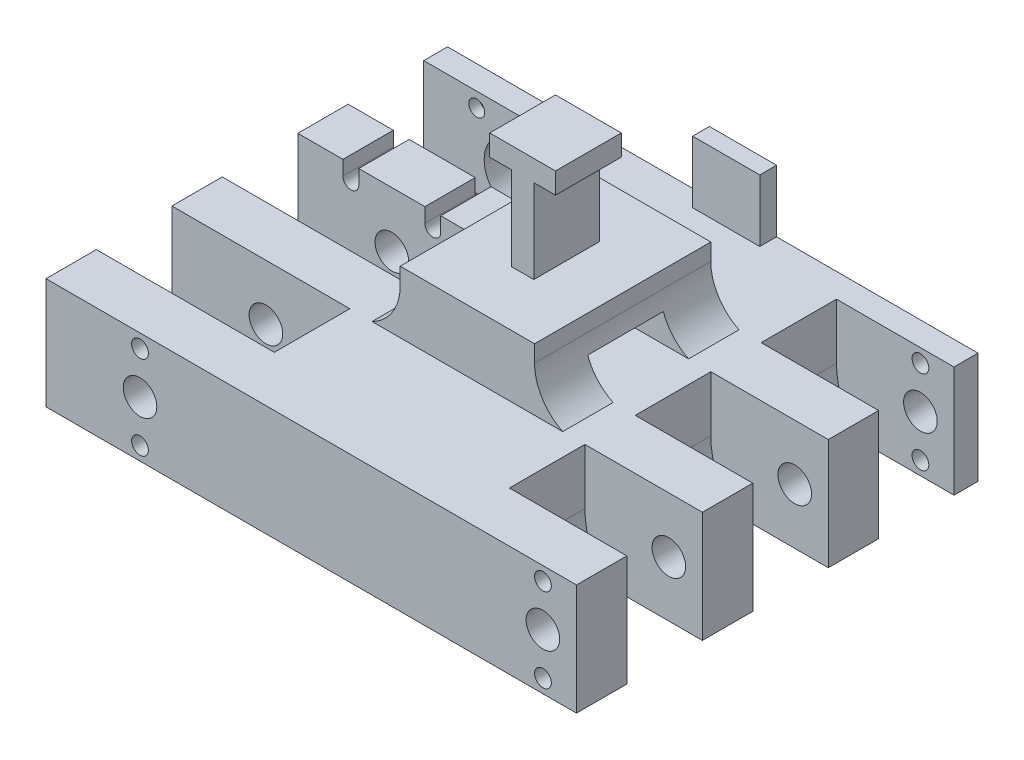
SolidWorks part; units mm, degrees
note: '?' marks a value the reader was unsure of. The reader was unsure of these and kept them because the rebuilt part matched: shared geometry of "Sketch17<3>", "Sketch17<5>", "Sketch17<6>", "Sketch2<4>", "Sketch2<5>".
ref_plane "Front Plane" through (0, 0, 0) normal (0, 0, 1) x (1, 0, 0)
ref_plane "Top Plane" through (0, 0, 0) normal (0, 1, 0) x (1, 0, 0)
ref_plane "Right Plane" through (0, 0, 0) normal (1, 0, 0) x (0, 0, -1)
sketch "Sketch1" plane through (0, 0, 0) normal (0, 1, 0) x (1, 0, 0)
  line L0 (-25.4, 0) -> (-25.4, 28.575)
  line L1 (-25.4, 123.825) -> (25.4, 123.825)
  line L2 (-25.4, 28.575) -> (-127, 28.575)
  line L3 (-25.4, 0) -> (25.4, 0)
  line L4 (0, 123.825) -> (0, 0) construction
  line L5 (-127, 28.575) -> (-127, 47.625)
  line L6 (-127, 47.625) -> (-25.4, 47.625)
  line L7 (-25.4, 47.625) -> (-25.4, 76.2)
  line L8 (-25.4, 76.2) -> (-127, 76.2)
  line L9 (-127, 76.2) -> (-127, 95.25)
  line L10 (-127, 95.25) -> (-25.4, 95.25)
  line L11 (-25.4, 95.25) -> (-25.4, 123.825)
  line L12 (25.4, 95.25) -> (25.4, 123.825)
  line L13 (127, 95.25) -> (25.4, 95.25)
  line L14 (127, 76.2) -> (127, 95.25)
  line L15 (25.4, 76.2) -> (127, 76.2)
  line L16 (25.4, 47.625) -> (25.4, 76.2)
  line L17 (127, 47.625) -> (25.4, 47.625)
  line L18 (127, 28.575) -> (127, 47.625)
  line L19 (25.4, 28.575) -> (127, 28.575)
  line L20 (25.4, 0) -> (25.4, 28.575)
  point P1 (-76.2, 28.575)
  dimension "D1" = 28.575
  dimension "D2" = 19.05
  dimension "D3" = 28.575
  dimension "D4" = 19.05
  dimension "D5" = 28.575
  dimension "D6" = 76.2
  dimension "D7" = 101.6
extrude "Boss-Extrude1" add sketch "Sketch1" along normal blind 38.1
sketch "Sketch2" plane through (0, 0, -28.575) normal (0, 0, 1) x (1, 0, 0)
  line L0 (-127, 38.1) -> (-127, 0) construction
  line L1 (-127, 0) -> (-25.4, 0) construction
  line L2 (0, 38.1) -> (0, 0) construction
  line L3 (-25.4, 38.1) -> (25.4, 38.1) construction
  circle A0 centre (-76.2, 19.05) radius 6.35
  circle A1 centre (76.2, 19.05) radius 6.35
  point P5 (-127, 19.05)
  point P8 (-76.2, 0)
  dimension "D1" = 12.7
extrude "Cut-Extrude1" cut sketch "Sketch2" against normal blind 254 and the other way through all contours A0 | A1
ref_plane "Plane1" through (0, 0, -61.9125) normal (0, 0, 1) x (1, 0, 0)
ref_axis "Axis3" through (0, 40.005, -61.9125) along (0, -1, 0)?
sketch "Sketch12" plane through (0, 38.1, 0) normal (0, 1, 0) x (1, 0, 0)
  line L1 (25.4, 28.575) -> (-25.4, 28.575)
  line L2 (25.4, 28.575) -> (25.4, 47.625)
  line L3 (25.4, 47.625) -> (-25.4, 47.625)
  line L4 (-25.4, 28.575) -> (-25.4, 47.625)
  line L5 (25.4, 76.2) -> (-25.4, 76.2)
  line L6 (25.4, 76.2) -> (25.4, 95.25)
  line L7 (25.4, 95.25) -> (-25.4, 95.25)
  line L8 (-25.4, 76.2) -> (-25.4, 95.25)
extrude "Boss-Extrude6" add sketch "Sketch12" along normal blind 12.7
sketch "Sketch13" plane through (0, 50.8, 0) normal (0, 1, 0) x (1, 0, 0)
  line L1 (25.4, 28.575) -> (-25.4, 28.575)
  line L2 (25.4, 28.575) -> (25.4, 95.25)
  line L3 (25.4, 95.25) -> (-25.4, 95.25)
  line L4 (-25.4, 28.575) -> (-25.4, 95.25)
extrude "Boss-Extrude7" add sketch "Sketch13" along normal blind 12.7
sketch "Sketch5" plane through (0, 63.5, 0) normal (0, 1, 0) x (1, 0, 0)
  line L1 (4.2333, 74.3585) -> (-4.2333, 74.3585)
  line L2 (4.2333, 74.3585) -> (4.2333, 49.4665)
  line L3 (4.2333, 49.4665) -> (-4.2333, 49.4665)
  line L4 (-4.2333, 74.3585) -> (-4.2333, 49.4665)
  point P4 (-4.2333, 61.9125)
  point P5 (0, 74.3585)
  dimension "D1" = 24.892
  dimension "D2" = 8.4667
extrude "Boss-Extrude8" add sketch "Sketch5" along normal blind 31.75 contours L4 L3 L2 L1
sketch "Sketch15" plane through (0, 95.25, 0) normal (0, 1, 0) x (1, 0, 0)
  line L1 (-12.446, 74.3585) -> (12.446, 74.3585)
  line L2 (-12.446, 74.3585) -> (-12.446, 49.4665)
  line L3 (-12.446, 49.4665) -> (12.446, 49.4665)
  line L4 (12.446, 74.3585) -> (12.446, 49.4665)
  point P4 (-12.446, 61.9125)
  point P6 (0, 49.4665)
  dimension "D1" = 24.892
  dimension "D2" = 24.892
extrude "Boss-Extrude9" add sketch "Sketch15" along normal blind 7.9375 contours L1 L4 L3 L2
sketch "Sketch17" plane through (0, 0, -123.825) normal (0, 0, -1) x (-1, 0, 0)
  line L0 (55.2, -1.95) -> (-25.4, -1.95)
  line L1 (60.7, 34.55) -> (91.7, 34.55) construction
  line L2 (60.7, 34.55) -> (60.7, 3.55) construction
  line L3 (60.7, 3.55) -> (91.7, 3.55) construction
  line L4 (91.7, 34.55) -> (91.7, 3.55) construction
  line L5 (55.2, 40.05) -> (97.2, 40.05)
  line L6 (-25.4, 38.1) -> (-25.4, 0) construction
  line L7 (55.2, -1.95) -> (97.2, -1.95)
  line L8 (97.2, 40.05) -> (97.2, -1.95)
  line L9 (55.2, 40.05) -> (97.2, -1.95) construction
  line L10 (55.2, -1.95) -> (97.2, 40.05) construction
  line L11 (60.7, 34.55) -> (91.7, 3.55) construction
  line L12 (60.7, 3.55) -> (91.7, 34.55) construction
  line L13 (-25.4, 40.05) -> (-25.4, -1.95)
  line L14 (-25.4, 63.5) -> (-25.4, 38.1) construction
  line L15 (-25.4, 40.05) -> (55.2, 40.05)
  circle A2 centre (76.2, 19.05) radius 6.35 construction
  circle A3 centre (76.2, 19.05) radius 12.7
  circle A4 centre (91.7, 34.55) radius 3
  circle A5 centre (60.7, 34.55) radius 3
  circle A6 centre (60.7, 3.55) radius 3
  circle A7 centre (91.7, 3.55) radius 3
  circle A8 centre (91.7, 3.55) radius 2
  circle A9 centre (60.7, 3.55) radius 2
  circle A10 centre (60.7, 34.55) radius 2
  circle A11 centre (91.7, 34.55) radius 2
  point P0 (76.2, 19.05)
  point P5 (76.2, 19.05)
  point P23 (97.2, 19.05)
  point P30 (-25.4, 19.05)
  point P31 (91.7, 19.05)
  dimension "D5" = 25.4
  dimension "D6" = 6
  dimension "D7" = 4
  dimension "D1" = 31
  dimension "D2" = 42
  dimension "D3" = 42
  dimension "D4" = 31
extrude "Boss-Extrude10" add sketch "Sketch17" along normal blind 9 contours L15 L5 L8 L7 L0 L13
extrude "Cut-Extrude2" cut sketch "Sketch17<3>" along normal through all contours A11 | A10 | A8 | A9
sketch "Sketch17<3>" plane through (0, 0, -123.825) normal (0, 0, -1) x (-1, 0, 0) same geometry as "Sketch17"
extrude "Cut-Extrude4" cut sketch "Sketch17<5>" along normal blind 4 and the other way up to surface contours A7 A8 | A4 | A5 | A6 other way up to face at (-82.55, 19.05, -76.2)
sketch "Sketch17<5>" plane through (0, 0, -123.825) normal (0, 0, -1) x (-1, 0, 0) same geometry as "Sketch17"
extrude "Cut-Extrude5" cut sketch "Sketch17<6>" along normal through all contours A3
sketch "Sketch17<6>" plane through (0, 0, -123.825) normal (0, 0, -1) x (-1, 0, 0) same geometry as "Sketch17"
sketch "Sketch18" plane through (0, 0, -76.2) normal (0, 0, 1) x (1, 0, 0)
  line L0 (-94.7, 34.55) -> (-88.7, 34.55)
  line L1 (-88.7, 34.55) -> (-88.7, 38.1)
  line L2 (-127, 38.1) -> (-25.4, 38.1) construction
  line L3 (-88.7, 38.1) -> (-94.7, 38.1)
  line L4 (-94.7, 38.1) -> (-94.7, 34.55)
  line L5 (-63.7, 34.55) -> (-57.7, 34.55)
  line L6 (-57.7, 34.55) -> (-57.7, 38.1)
  line L7 (-57.7, 38.1) -> (-63.7, 38.1)
  line L8 (-63.7, 38.1) -> (-63.7, 34.55)
  line L9 (-94.7, 3.55) -> (-88.7, 3.55)
  line L10 (-94.7, 3.55) -> (-94.7, 0)
  line L11 (-88.7, 3.55) -> (-88.7, 0)
  line L12 (-94.7, 0) -> (-88.7, 0)
  line L13 (-127, 0) -> (-25.4, 0) construction
  line L14 (-63.7, 3.55) -> (-57.7, 3.55)
  line L15 (-63.7, 3.55) -> (-63.7, 0)
  line L16 (-57.7, 3.55) -> (-57.7, 0)
  line L17 (-63.7, 0) -> (-57.7, 0)
  circle A0 centre (-91.7, 34.55) radius 3 construction
  circle A1 centre (-91.7, 34.55) radius 3 construction
  circle A2 centre (-60.7, 34.55) radius 3 construction
  circle A3 centre (-60.7, 34.55) radius 3 construction
  circle A4 centre (-91.7, 3.55) radius 3 construction
  circle A5 centre (-91.7, 3.55) radius 3 construction
  circle A6 centre (-60.7, 3.55) radius 3 construction
  circle A7 centre (-60.7, 3.55) radius 3 construction
extrude "Cut-Extrude6" cut sketch "Sketch18" against normal up to surface (19.05 mm away) contours L1 L3 L4 L0 | L8 L5 L6 L7 | L10 L12 L11 L9 | L15 L17 L16 L14 up to face at (-88.7, 34.55, -95.25)
sketch "Sketch19" plane through (0, 0, 0) normal (0, 0, 1) x (1, 0, 0)
  line L1 (-127, 38.1) -> (127, 38.1)
  line L2 (-127, 38.1) -> (-127, 0)
  line L3 (-127, 0) -> (127, 0)
  line L4 (127, 38.1) -> (127, 0)
extrude "Boss-Extrude11" add sketch "Sketch19" along normal blind 19.05
extrude "Cut-Extrude7" cut sketch "Sketch2<4>" along normal through all contours A1 | A0
sketch "Sketch2<4>" plane through (0, 0, -28.575) normal (0, 0, 1) x (1, 0, 0) same geometry as "Sketch2"
fillet "Fillet4" radius 19.05 2 edges at (25.4, 38.1, -38.1) (-25.4, 38.1, -85.725)
chamfer "Chamfer1" distance 2.032 angle 45 4 edges at (25.4, 39.075, -123.825) (25.4, -0.975, -123.825) (0, 0, -123.825) (0, 38.1, -123.825)
fillet "Fillet1" radius 6.35 1 edges at (-25.4, 19.05, -123.825)
sketch "Sketch28" plane through (0, 38.1, 0) normal (0, 1, 0) x (1, 0, 0)
  line L1 (-127, 0) -> (127, 0)
  line L2 (-127, 0) -> (-127, -19.05)
  line L3 (-127, -19.05) -> (127, -19.05)
  line L4 (127, 0) -> (127, -19.05)
extrude "Boss-Extrude15" add sketch "Sketch28" along normal up to surface (1.95 mm away) up to face at (-34.3469, 40.05, -126.8011)
sketch "Sketch30" plane through (0, 0, 0) normal (0, -1, 0) x (1, 0, 0)
  line L1 (-127, 19.05) -> (127, 19.05)
  line L2 (-127, 19.05) -> (-127, 0)
  line L3 (-127, 0) -> (127, 0)
  line L4 (127, 19.05) -> (127, 0)
extrude "Boss-Extrude18" add sketch "Sketch30" along normal up to surface (1.95 mm away) up to face at (-34.3469, -1.95, -126.8011)
sketch "Sketch20" plane through (0, 0, 19.05) normal (0, 0, 1) x (1, 0, 0)
  circle A0 centre (76.2, 3.175) radius 3.175
  circle A1 centre (76.2, 34.925) radius 3.175
  circle A5 centre (76.2, 19.05) radius 6.35 construction
  point P8 (76.2, 19.05)
  dimension "D1" = 6.35
  dimension "D2" = 6.35
  dimension "D3" = 15.875
  dimension "D4" = 15.875
extrude "Cut-Extrude8" cut sketch "Sketch20" against normal blind 9.525 contours A0 | A1
mirror "Mirror1" about plane through (0, 0, 0) normal (1, 0, 0) of "Cut-Extrude8"
sketch "Sketch23" plane through (25.4, 0, 0) normal (1, 0, 0) x (0, 0, -1)
  line L1 (132.825, 40.05) -> (123.743, 40.05)
  line L2 (132.825, 40.05) -> (132.825, -1.95)
  line L3 (132.825, -1.95) -> (123.743, -1.95)
  line L4 (123.743, 40.05) -> (123.743, -1.95)
  line L5 (128.284, -1.95) -> (128.284, 40.05) construction
  line L6 (132.825, 19.05) -> (123.743, 19.05) construction
  point P256 (128.284, 19.05)
extrude "Boss-Extrude12" add sketch "Sketch23" along normal up to surface (101.6 mm away) up to face at (127, 19.05, -85.725)
sketch "Sketch22" plane through (0, 0, -132.825) normal (0, 0, -1) x (-1, 0, 0)
  circle A0 centre (-76.2, 3.175) radius 3.175
  circle A1 centre (-76.2, 34.925) radius 3.175
  circle A2 centre (-76.2, 19.05) radius 6.35 construction
  point P4 (-76.2, 19.05)
  point P8 (-76.2, 19.05)
  dimension "D1" = 6.35
  dimension "D2" = 6.35
  dimension "D3" = 15.875
  dimension "D4" = 15.875
extrude "Cut-Extrude9" cut sketch "Sketch22" against normal blind 9.525 contours A0 | A1
extrude "Cut-Extrude10" cut sketch "Sketch2<5>" against normal up to surface (104.25 mm away) up to face at (73.025, 34.925, -132.825)
sketch "Sketch2<5>" plane through (0, 0, -28.575) normal (0, 0, 1) x (1, 0, 0) same geometry as "Sketch2"
fillet "Fillet2" radius 6.35 11 edges at (25.4, 19.05, -95.25) (25.4, 19.05, -47.625) (25.4, 19.05, -76.2) (25.4, 19.05, -28.575) (-25.4, 19.05, -28.575) (-25.4, 19.05, -47.625) (-25.4, 19.05, -76.2) (-25.4, 19.05, -95.25) (25.4, 19.05, 0) (-25.4, 19.05, 0) (25.4, 19.05, -123.743)
sketch "Sketch25" plane through (-97.2, 0, 0) normal (-1, 0, 0) x (0, 0, 1)
  line L1 (-132.825, 40.05) -> (-123.825, 40.05)
  line L2 (-132.825, 40.05) -> (-132.825, -1.95)
  line L3 (-132.825, -1.95) -> (-123.825, -1.95)
  line L4 (-123.825, 40.05) -> (-123.825, -1.95)
  line L5 (-128.325, -1.95) -> (-128.325, 40.05) construction
  line L6 (-132.825, 19.05) -> (-123.825, 19.05) construction
  point P124 (-128.325, 19.05)
extrude "Boss-Extrude13" add sketch "Sketch25" along normal up to surface (29.8 mm away) up to face at (-127, 19.05, -85.725)
sketch "Sketch26" plane through (0, 0, 0) normal (0, 0, -1) x (-1, 0, 0)
  line L0 (-44.45, 40.05) -> (0, 40.05)
  line L1 (-127, 40.05) -> (127, 40.05) construction
  line L2 (0, 40.05) -> (0, -1.95)
  line L3 (-127, -1.95) -> (127, -1.95) construction
  line L4 (0, -1.95) -> (-52.3869, -1.95)
  line L5 (-44.45, 19.05) -> (-44.45, 40.05)
  line L6 (0, 20.955) -> (0, -20.955) construction
  circle A0 centre (-76.2, 19.05) radius 6.35 construction
  arc A1 (-44.45, 19.05) -> (-52.3869, -1.95) centre (-76.2, 19.05) cw
  arc A2 (-52.3869, 40.05) -> (-44.45, 19.05) centre (-76.2, 19.05) ccw construction
  point P340 (-76.2, 19.05)
  line M2 (31.75, 0) -> (-31.75, 0)
  line M3 (-31.75, 0) -> (-31.75, 38.1)
  line M4 (-31.75, 38.1) -> (31.75, 38.1)
  line M33 (127, 40.05) -> (-127, 40.05)
  line M35 (-127, -1.95) -> (127, -1.95)
  dimension "D1" = 63.5
extrude "Boss-Extrude19" add sketch "Sketch26" along normal up to surface (132.825 mm away) contours A1 L2 M33 M35 M2 M3 M4 | L2 M4 M3 M2 up to face at (82.55, 19.05, -132.825)
mirror "Mirror2" about plane through (0, 0, 0) normal (1, 0, 0) of "Boss-Extrude19"
sketch "Sketch32" plane through (0, 38.1, 0) normal (0, 1, 0) x (1, 0, 0)
  line L0 (-94.7, 95.25) -> (-94.7, 76.2) construction
  line L1 (-127, 95.25) -> (-94.7, 95.25)
  line L2 (-127, 95.25) -> (-127, 76.2)
  line L3 (-127, 76.2) -> (-94.7, 76.2)
  line L4 (-94.7, 95.25) -> (-94.7, 76.2)
  line L5 (-127, 76.2) -> (-94.7, 76.2) construction
  line L7 (-88.7, 95.25) -> (-63.7, 95.25)
  line L8 (-88.7, 95.25) -> (-88.7, 76.2)
  line L9 (-88.7, 76.2) -> (-63.7, 76.2)
  line L10 (-63.7, 95.25) -> (-63.7, 76.2)
  line L11 (-57.7, 95.25) -> (-44.45, 95.25)
  line L12 (-57.7, 95.25) -> (-57.7, 76.2)
  line L13 (-57.7, 76.2) -> (-44.45, 76.2)
  line L14 (-44.45, 95.25) -> (-44.45, 76.2)
  line L15 (-44.45, 47.625) -> (-127, 47.625)
  line L16 (-44.45, 47.625) -> (-44.45, 28.575)
  line L17 (-44.45, 28.575) -> (-127, 28.575)
  line L18 (-127, 47.625) -> (-127, 28.575)
  line L19 (44.45, 47.625) -> (127, 47.625)
  line L20 (44.45, 47.625) -> (44.45, 28.575)
  line L21 (44.45, 28.575) -> (127, 28.575)
  line L22 (127, 47.625) -> (127, 28.575)
  line L23 (44.45, 95.25) -> (127, 95.25)
  line L24 (44.45, 95.25) -> (44.45, 76.2)
  line L25 (44.45, 76.2) -> (127, 76.2)
  line L26 (127, 95.25) -> (127, 76.2)
extrude "Boss-Extrude20" add sketch "Sketch32" along normal up to surface (1.95 mm away) up to face at (0, 40.05, -60.2238)
sketch "Sketch36" plane through (0, 0, 0) normal (0, -1, 0) x (1, 0, 0)
  line L1 (-127, -28.575) -> (127, -28.575)
  line L2 (-127, -28.575) -> (-127, -47.625)
  line L3 (-127, -47.625) -> (127, -47.625)
  line L4 (127, -28.575) -> (127, -47.625)
  line L5 (-57.7, -76.2) -> (127, -76.2)
  line L6 (-57.7, -76.2) -> (-57.7, -95.25)
  line L7 (-57.7, -95.25) -> (127, -95.25)
  line L8 (127, -76.2) -> (127, -95.25)
  line L9 (-94.7, -76.2) -> (-127, -76.2)
  line L10 (-94.7, -76.2) -> (-94.7, -95.25)
  line L11 (-94.7, -95.25) -> (-127, -95.25)
  line L12 (-127, -76.2) -> (-127, -95.25)
  line L13 (-88.7, -76.2) -> (-63.7, -76.2)
  line L14 (-88.7, -76.2) -> (-88.7, -95.25)
  line L15 (-88.7, -95.25) -> (-63.7, -95.25)
  line L16 (-63.7, -76.2) -> (-63.7, -95.25)
extrude "Boss-Extrude26" add sketch "Sketch36" along normal up to surface (1.95 mm away) up to face at (0, -1.95, -60.2238)
sketch "Sketch37" plane through (127, 0, 0) normal (1, 0, 0) x (0, 0, -1)
  line L1 (-19.05, 40.05) -> (0, 40.05)
  line L2 (-19.05, 40.05) -> (-19.05, -1.95)
  line L3 (-19.05, -1.95) -> (0, -1.95)
  line L4 (0, 40.05) -> (0, -1.95)
  line L5 (28.575, 40.05) -> (47.625, 40.05)
  line L6 (28.575, 40.05) -> (28.575, -1.95)
  line L7 (28.575, -1.95) -> (47.625, -1.95)
  line L8 (47.625, 40.05) -> (47.625, -1.95)
  line L9 (76.2, 40.05) -> (95.25, 40.05)
  line L10 (76.2, 40.05) -> (76.2, -1.95)
  line L11 (76.2, -1.95) -> (95.25, -1.95)
  line L12 (95.25, 40.05) -> (95.25, -1.95)
  line L13 (123.743, 40.05) -> (132.825, 40.05)
  line L14 (123.743, 40.05) -> (123.743, -1.95)
  line L15 (123.743, -1.95) -> (132.825, -1.95)
  line L16 (132.825, 40.05) -> (132.825, -1.95)
extrude "Cut-Extrude11" cut sketch "Sketch37" against normal blind 38.1
sketch "Sketch39" plane through (-127, 0, 0) normal (-1, 0, 0) x (0, 0, 1)
  line L1 (-132.825, 40.05) -> (-123.825, 40.05)
  line L2 (-132.825, 40.05) -> (-132.825, -1.95)
  line L3 (-132.825, -1.95) -> (-123.825, -1.95)
  line L4 (-123.825, 40.05) -> (-123.825, -1.95)
  line L5 (-95.25, 40.05) -> (-76.2, 40.05)
  line L6 (-95.25, 40.05) -> (-95.25, -1.95)
  line L7 (-95.25, -1.95) -> (-76.2, -1.95)
  line L8 (-76.2, 40.05) -> (-76.2, -1.95)
  line L9 (-47.625, 40.05) -> (-28.575, 40.05)
  line L10 (-47.625, 40.05) -> (-47.625, -1.95)
  line L11 (-47.625, -1.95) -> (-28.575, -1.95)
  line L12 (-28.575, 40.05) -> (-28.575, -1.95)
  line L13 (0, 40.05) -> (19.05, 40.05)
  line L14 (0, 40.05) -> (0, -1.95)
  line L15 (0, -1.95) -> (19.05, -1.95)
  line L16 (19.05, 40.05) -> (19.05, -1.95)
extrude "Cut-Extrude12" cut sketch "Sketch39" against normal blind 15.24
sketch "Sketch40" plane through (0, 40.05, 0) normal (0, 1, 0) x (1, 0, 0)
  line L0 (25.4, 95.25) -> (-25.4, 95.25) construction
  line L1 (-12.7, 132.825) -> (12.7, 132.825)
  line L2 (-12.7, 132.825) -> (-12.7, 126.475)
  line L3 (-12.7, 126.475) -> (12.7, 126.475)
  line L4 (12.7, 132.825) -> (12.7, 126.475)
  line L5 (88.9, 132.825) -> (-111.76, 132.825) construction
  point P4 (0, 132.825)
  point P7 (0, 95.25)
  dimension "D1" = 25.4
  dimension "D2" = 6.35
extrude "Boss-Extrude27" add sketch "Sketch40" along normal up to surface (23.45 mm away) up to face at (0, 63.5, -61.9125)
